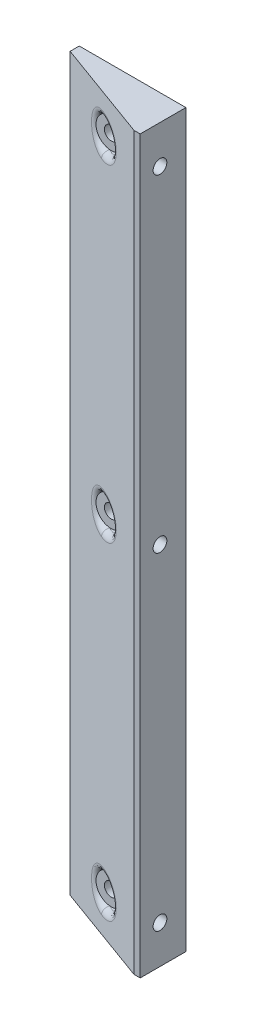
SolidWorks part; units mm, degrees
ref_plane "Front Plane" through (0, 0, 0) normal (0, 0, 1) x (1, 0, 0)
ref_plane "Top Plane" through (0, 0, 0) normal (0, 1, 0) x (1, 0, 0)
ref_plane "Right Plane" through (0, 0, 0) normal (1, 0, 0) x (0, 0, -1)
sketch "Sketch1" plane through (0, 0, 0) normal (0, 0, 1) x (1, 0, 0)
  line L5 (-17.5, -120) -> (17.5, -120)
  line L6 (-17.5, -120) -> (-17.5, 120)
  line L7 (-17.5, 120) -> (17.5, 120)
  line L8 (17.5, -120) -> (17.5, 120)
  line L9 (-17.5, -120) -> (17.5, 120) construction
  line L10 (-17.5, 120) -> (17.5, -120) construction
  point P0 (0, 0)
  dimension "D1" = 35
  dimension "D2" = 240
extrude "Boss-Extrude1" add sketch "Sketch1" along normal blind 15
sketch "Sketch2" plane through (0, 0, 0) normal (0, 0, -1) x (-1, 0, 0)
  circle A0 centre (0, 107.5) radius 2.25
  circle A1 centre (0, 0) radius 2.25
  circle A2 centre (0, -107.5) radius 2.25
  point P7 (0, 0)
  dimension "D1" = 4.5
  dimension "D2" = 107.5
  dimension "D3" = 107.5
extrude "Cut-Extrude1" cut sketch "Sketch2" against normal blind 20
chamfer "Chamfer1" distance 12 angle 70 1 edges at (-17.5, 0, 15) first distance on face at (-17.5, 0, 7.5)
ref_plane "Plane1" through (0, 0, 7) normal (0, 0, -1) x (-1, 0, 0)
sketch "Sketch3" plane through (0, 0, 7) normal (0, 0, -1) x (-1, 0, 0)
  circle A0 centre (0, 107.5) radius 5
  circle A1 centre (0, 0) radius 5
  circle A2 centre (0, -107.5) radius 5
  dimension "D1" = 10
  dimension "D2" = 10
  dimension "D3" = 10
extrude "Cut-Extrude2" cut sketch "Sketch3" against normal blind 5
fillet "Fillet1" radius 2 3 edges at (-5, 107.5, 7.5496) (-5, -107.5, 7.5496) (-5, 0, 7.5496)
sketch "Sketch5" plane through (17.5, 0, 0) normal (1, 0, 0) x (0, 0, -1)
  line L1 (0, -120) -> (0, 120) construction
  circle A0 centre (-8.5, 107.5) radius 2.25
  circle A1 centre (-8.5, 0) radius 2.25
  circle A2 centre (-8.5, -107.5) radius 2.25
  point P6 (-9.5145, 107.4952)
  point P7 (0, 0)
  point P8 (-7, -98.7974)
  point P9 (-7, -105.8069)
  point P10 (-7, 0)
  point P11 (-7, 108.928)
  point P12 (-7, 113.4281)
  point P13 (0, 0)
  point P15 (-9.8309, 0)
  point P16 (-8.7797, 0)
  point P19 (-10.6805, -107.4779)
  dimension "D1" = 107.5
  dimension "D3" = 4.5
  dimension "D2" = 107.5
  dimension "D4" = 8.5
extrude "Cut-Extrude3" cut sketch "Sketch5" against normal blind 5
